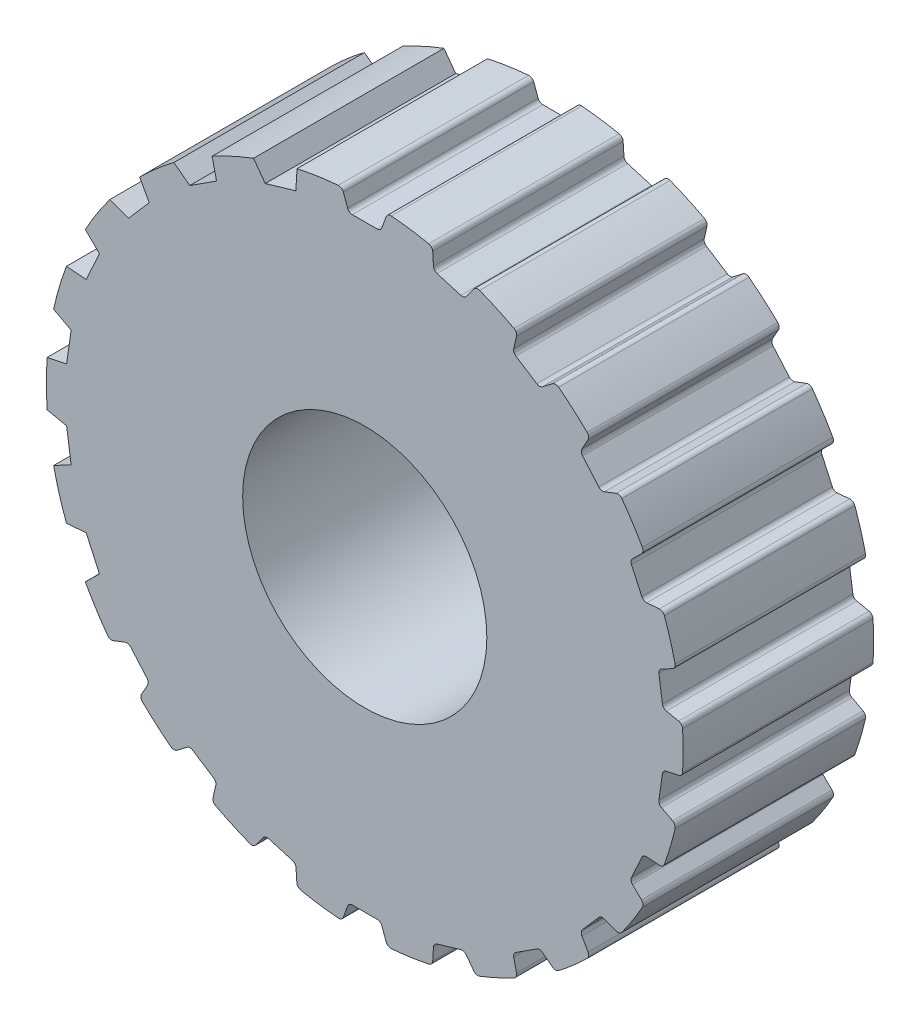
SolidWorks part; units mm, degrees
ref_plane "Front Plane" through (0, 0, 0) normal (0, 0, 1) x (1, 0, 0)
ref_plane "Top Plane" through (0, 0, 0) normal (0, 1, 0) x (1, 0, 0)
ref_plane "Right Plane" through (0, 0, 0) normal (1, 0, 0) x (0, 0, -1)
sketch "Sketch1" plane through (0, 0, 0) normal (0, 1, 0) x (1, 0, 0)
  line L0 (0, 36.1296) -> (0, -19.4741) construction
sketch "Sketch7" plane through (0, 0, 0) normal (0, 0, 1) x (1, 0, 0)
  line L0 (0, 0) -> (0, 31.56) construction
  line L1 (-2.325, 32.515) -> (-2.9401, 34.205) construction
  line L2 (-2.325, 32.515) -> (-1.6298, 30.605) construction
  line L3 (-1.6298, 30.605) -> (1.6298, 30.605) construction
  line L4 (1.6298, 30.605) -> (2.325, 32.515) construction
  line L5 (2.325, 32.515) -> (-2.325, 32.515) construction
  line L6 (0, 30.605) -> (0, 32.515) construction
  line L7 (2.325, 32.515) -> (2.9401, 34.205) construction
  line L8 (-2.9401, 34.205) -> (2.9401, 34.205) construction
  line L9 (0, 0) -> (8.8915, 30.2816) construction
  line L10 (8.8915, 30.2816) -> (9.1839, 31.2775) construction
  line L11 (0, 32.515) -> (0, 32.598) construction
  line L12 (0, 32.598) -> (0, 34.3311) construction
  line L13 (0, 33.4645) -> (9.428, 32.109) construction
  line L14 (9.1839, 31.2775) -> (9.6722, 32.9404) construction
  circle A1 centre (0, 0) radius 31.56 construction
  circle A2 centre (-1.2727, 31.115) radius 0.51 construction
  circle A3 centre (1.2727, 31.115) radius 0.51 construction
  circle A4 centre (0, 0) radius 32.598
  circle A5 centre (0, 0) radius 34.3311 construction
  dimension "D3" = 40
  dimension "D6" = 1.02
  dimension "D1" = 3.6
  dimension "D2" = 16.364
  dimension "D7" = 9.525
  dimension "D4" = 1.91
  dimension "D5" = 4.65
extrude "Boss-Extrude1" add sketch "Sketch7" along normal blind 7.25 and the other way blind 7.25 contours A4 region at (0, 0, 0)
sketch "Sketch14" plane through (0, 0, 0) normal (1, 0, 0) x (0, 0, -1)
  line L0 (-21.5, 0) -> (-21.5, 10)
  line L1 (-21.5, 0) -> (0, 0)
  line L2 (0, 0) -> (0, 19)
  line L3 (0, 19) -> (-7.25, 19)
  line L4 (-7.25, 19) -> (-21.5, 10)
  line L5 (-7.25, 32.598) -> (-7.25, -32.598) construction
  line L6 (-21.5, 7.0431) -> (-2.5683, 19) construction
  arc A0 (-7.25, 19) -> (-21.5, 10) centre (-21.2919, 25.4517) cw
  dimension "D1" = 10
  dimension "D2" = 19
  dimension "D3" = 21.5
  dimension "D4" = 2.5
revolve "Revolve1" add sketch "Sketch14" angle 360 about L0 region at (0, 7.3866, 9.0486) region at (0, 9.3218, 19.3148) region at (0, 17.2024, 6.8722)
sketch "Sketch9" plane through (0, 0, 0) normal (0, 0, 1) x (1, 0, 0)
  line L0 (2, 0) -> (-2, 0) construction
  line L1 (-2, 0) -> (-2, 7.5) construction
  line L2 (-2, 7.5) -> (2, 7.5) construction
  line L3 (2, 7.5) -> (2, 0) construction
  circle A0 centre (0, 0) radius 6 construction
  dimension "D1" = 12
  dimension "D2" = 4
  dimension "D3" = 7.5
sketch "Sketch10" plane through (0, 0, 0) normal (0, 0, 1) x (1, 0, 0)
  line L0 (2, 0) -> (-2, 0) construction
  line L1 (-2.2, 7.7) -> (2.2, 7.7)
  line L2 (-2.2, 7.7) -> (-2.2, 0)
  line L3 (-2.2, 0) -> (2.2, 0)
  line L4 (2.2, 7.7) -> (2.2, 0)
  line L5 (-2, 7.5) -> (2, 7.5) construction
  line L6 (2, 7.5) -> (2, 0) construction
  circle A0 centre (0, 0) radius 6.2
  circle A1 centre (0, 0) radius 6 construction
  dimension "D1" = 0.2
  dimension "D2" = 0.2
  dimension "D3" = 0.2
extrude "Cut-Extrude3" cut sketch "Sketch10" against normal through all both and the other way through all contours A0 L4 L1 L2 | L2 A0 L4 L3 | L4 A0 L2 L3 region at (0, 6.8793, 0) region at (0, 3.0348, 0) region at (0, -0.8613, 0)
sketch "Sketch11" plane through (0, 0, 0) normal (0, 1, 0) x (1, 0, 0)
  line L0 (32.598, 7.25) -> (-32.598, 7.25) construction
  line L1 (11, 7.25) -> (17.5, 7.25)
  line L2 (11, 7.25) -> (11, 4.75)
  line L3 (11, 4.75) -> (17.5, 4.75)
  line L4 (17.5, 7.25) -> (17.5, 4.75)
  line L5 (-32.598, -7.25) -> (32.598, -7.25) construction
  line L6 (11, -7.25) -> (17.5, -7.25)
  line L7 (11, -7.25) -> (11, -4.75)
  line L8 (11, -4.75) -> (17.5, -4.75)
  line L9 (17.5, -7.25) -> (17.5, -4.75)
  line L11 (11, 4.75) -> (11, -4.75) construction
  line L12 (17.5, -4.75) -> (17.5, 4.75) construction
  line L13 (6.2, 7.25) -> (-6.2, 7.25) construction
  line L14 (0, 7.25) -> (22.5, 7.25)
  line L15 (0, 7.25) -> (0, -7.25)
  line L16 (0, -7.25) -> (22.5, -7.25)
  line L17 (22.5, 7.25) -> (22.5, -7.25)
  line L18 (-6.2, -7.25) -> (6.2, -7.25) construction
  line L19 (6, 7.25) -> (6, -7.25) construction
  dimension "D1" = 22.5
  dimension "D2" = 6
  dimension "D3" = 5
  dimension "D4" = 5
  dimension "D5" = 2.5
revolve "Cut-Revolve1" [suppressed] cut sketch "Sketch11" angle 360 about L0
sketch "Sketch15" plane through (0, 0, -7.25) normal (0, 0, -1) x (-1, 0, 0)
  circle A0 centre (0, 0) radius 8.0081
  circle A1 centre (0, 0) radius 2.25
  dimension "D1" = 4.5
extrude "Boss-Extrude2" add sketch "Sketch15" against normal blind 5.5
sketch "Sketch16" plane through (0, 0, -7.25) normal (0, 0, -1) x (-1, 0, 0)
  circle A0 centre (0, 0) radius 5
  dimension "D1" = 10
extrude "Cut-Extrude4" cut sketch "Sketch16" against normal blind 3
sketch "Sketch17" plane through (0, 0, -7.25) normal (0, 0, -1) x (-1, 0, 0)
  circle A0 centre (0, 0) radius 32.598
  circle A1 centre (0, 0) radius 32.598 construction
  circle A2 centre (0, 0) radius 5
  circle A3 centre (0, 0) radius 5 construction
extrude "Boss-Extrude3" add sketch "Sketch17" along normal blind 7.5
sketch "Sketch8" plane through (0, 0, 0) normal (0, 0, 1) x (1, 0, 0)
  line L6 (-1.6298, 30.605) -> (-2.3552, 32.598)
  line L7 (-2.3552, 32.598) -> (2.3552, 32.598)
  line L8 (2.3552, 32.598) -> (1.6298, 30.605)
  line L9 (1.6298, 30.605) -> (-1.6298, 30.605)
  line L10 (-2.325, 32.515) -> (-1.6298, 30.605) construction
  line L11 (1.6298, 30.605) -> (2.325, 32.515) construction
  line L12 (7.0586, 29.8244) -> (6.9241, 31.9411)
  line L13 (6.9241, 31.9411) -> (11.4437, 30.614)
  line L14 (11.4437, 30.614) -> (10.1862, 28.9061)
  line L15 (10.1862, 28.9061) -> (7.0586, 29.8244)
  line L16 (15.1752, 26.6277) -> (15.6425, 28.6965)
  line L17 (15.6425, 28.6965) -> (19.6051, 26.1498)
  line L18 (19.6051, 26.1498) -> (17.9174, 24.8654)
  line L19 (17.9174, 24.8654) -> (15.1752, 26.6277)
  line L20 (22.0624, 21.2737) -> (23.0936, 23.1271)
  line L21 (23.0936, 23.1271) -> (26.1782, 19.5672)
  line L22 (26.1782, 19.5672) -> (24.197, 18.8103)
  line L23 (24.197, 18.8103) -> (22.0624, 21.2737)
  line L24 (27.1622, 14.1963) -> (28.6738, 15.6841)
  line L25 (28.6738, 15.6841) -> (30.6306, 11.3993)
  line L26 (30.6306, 11.3993) -> (28.5163, 11.2312)
  line L27 (28.5163, 11.2312) -> (27.1622, 14.1963)
  line L28 (30.0615, 5.9688) -> (31.931, 6.9704)
  line L29 (31.931, 6.9704) -> (32.6014, 2.3079)
  line L30 (32.6014, 2.3079) -> (30.5254, 2.7423)
  line L31 (30.5254, 2.7423) -> (30.0615, 5.9688)
  line L32 (30.5254, -2.7423) -> (32.6014, -2.3079)
  line L33 (32.6014, -2.3079) -> (31.931, -6.9704)
  line L34 (31.931, -6.9704) -> (30.0615, -5.9688)
  line L35 (30.0615, -5.9688) -> (30.5254, -2.7423)
  line L36 (28.5163, -11.2312) -> (30.6306, -11.3993)
  line L37 (30.6306, -11.3993) -> (28.6738, -15.6841)
  line L38 (28.6738, -15.6841) -> (27.1622, -14.1963)
  line L39 (27.1622, -14.1963) -> (28.5163, -11.2312)
  line L40 (24.197, -18.8103) -> (26.1782, -19.5672)
  line L41 (26.1782, -19.5672) -> (23.0936, -23.1271)
  line L42 (23.0936, -23.1271) -> (22.0624, -21.2737)
  line L43 (22.0624, -21.2737) -> (24.197, -18.8103)
  line L44 (17.9174, -24.8654) -> (19.6051, -26.1498)
  line L45 (19.6051, -26.1498) -> (15.6425, -28.6965)
  line L46 (15.6425, -28.6965) -> (15.1752, -26.6277)
  line L47 (15.1752, -26.6277) -> (17.9174, -24.8654)
  line L48 (10.1862, -28.9061) -> (11.4437, -30.614)
  line L49 (11.4437, -30.614) -> (6.9241, -31.9411)
  line L50 (6.9241, -31.9411) -> (7.0586, -29.8244)
  line L51 (7.0586, -29.8244) -> (10.1862, -28.9061)
  line L52 (1.6298, -30.605) -> (2.3552, -32.598)
  line L53 (2.3552, -32.598) -> (-2.3552, -32.598)
  line L54 (-2.3552, -32.598) -> (-1.6298, -30.605)
  line L55 (-1.6298, -30.605) -> (1.6298, -30.605)
  line L56 (-7.0586, -29.8244) -> (-6.9241, -31.9411)
  line L57 (-6.9241, -31.9411) -> (-11.4437, -30.614)
  line L58 (-11.4437, -30.614) -> (-10.1862, -28.9061)
  line L59 (-10.1862, -28.9061) -> (-7.0586, -29.8244)
  line L60 (-15.1752, -26.6277) -> (-15.6425, -28.6965)
  line L61 (-15.6425, -28.6965) -> (-19.6051, -26.1498)
  line L62 (-19.6051, -26.1498) -> (-17.9174, -24.8654)
  line L63 (-17.9174, -24.8654) -> (-15.1752, -26.6277)
  line L64 (-22.0624, -21.2737) -> (-23.0936, -23.1271)
  line L65 (-23.0936, -23.1271) -> (-26.1782, -19.5672)
  line L66 (-26.1782, -19.5672) -> (-24.197, -18.8103)
  line L67 (-24.197, -18.8103) -> (-22.0624, -21.2737)
  line L68 (-27.1622, -14.1963) -> (-28.6738, -15.6841)
  line L69 (-28.6738, -15.6841) -> (-30.6306, -11.3993)
  line L70 (-30.6306, -11.3993) -> (-28.5163, -11.2312)
  line L71 (-28.5163, -11.2312) -> (-27.1622, -14.1963)
  line L72 (-30.0615, -5.9688) -> (-31.931, -6.9704)
  line L73 (-31.931, -6.9704) -> (-32.6014, -2.3079)
  line L74 (-32.6014, -2.3079) -> (-30.5254, -2.7423)
  line L75 (-30.5254, -2.7423) -> (-30.0615, -5.9688)
  line L76 (-30.5254, 2.7423) -> (-32.6014, 2.3079)
  line L77 (-32.6014, 2.3079) -> (-31.931, 6.9704)
  line L78 (-31.931, 6.9704) -> (-30.0615, 5.9688)
  line L79 (-30.0615, 5.9688) -> (-30.5254, 2.7423)
  line L80 (-28.5163, 11.2312) -> (-30.6306, 11.3993)
  line L81 (-30.6306, 11.3993) -> (-28.6738, 15.6841)
  line L82 (-28.6738, 15.6841) -> (-27.1622, 14.1963)
  line L83 (-27.1622, 14.1963) -> (-28.5163, 11.2312)
  line L84 (-24.197, 18.8103) -> (-26.1782, 19.5672)
  line L85 (-26.1782, 19.5672) -> (-23.0936, 23.1271)
  line L86 (-23.0936, 23.1271) -> (-22.0624, 21.2737)
  line L87 (-22.0624, 21.2737) -> (-24.197, 18.8103)
  line L88 (-17.9174, 24.8654) -> (-19.6051, 26.1498)
  line L89 (-19.6051, 26.1498) -> (-15.6425, 28.6965)
  line L90 (-15.6425, 28.6965) -> (-15.1752, 26.6277)
  line L91 (-15.1752, 26.6277) -> (-17.9174, 24.8654)
  line L92 (-10.1862, 28.9061) -> (-11.4437, 30.614)
  line L93 (-11.4437, 30.614) -> (-6.9241, 31.9411)
  line L94 (-6.9241, 31.9411) -> (-7.0586, 29.8244)
  line L95 (-7.0586, 29.8244) -> (-10.1862, 28.9061)
  circle A0 centre (0, 0) radius 32.598 construction
  point P119 (0, 0)
  dimension "D1" = 22
extrude "Cut-Extrude2" cut sketch "Sketch8" against normal through all both and the other way through all
fillet "Fillet2" radius 0.51 60 edges at (-26.0957, -19.5357, -3.75) (-23.0506, -23.0499, -3.75) (-19.5348, -26.0963, -3.75) (-15.623, -28.6103, -3.75) (-11.3913, -30.5429, -3.75) (-6.9297, -31.8529, -3.75) (-2.325, -32.515, -3.75) (2.325, -32.515, -3.75) (6.9297, -31.8529, -3.75) (11.3913, -30.5429, -3.75) (15.623, -28.6103, -3.75) (19.5348, -26.0963, -3.75) (23.0506, -23.0499, -3.75) (26.0957, -19.5357, -3.75) (28.6108, -15.6221, -3.75) (30.5425, -11.3923, -3.75) (31.8531, -6.9287, -3.75) (32.5149, -2.326, -3.75) (32.5149, 2.326, -3.75) (31.8531, 6.9287, -3.75) (30.5425, 11.3923, -3.75) (28.6108, 15.6221, -3.75) (26.0957, 19.5357, -3.75) (23.0506, 23.0499, -3.75) (19.5348, 26.0963, -3.75) (15.623, 28.6103, -3.75) (11.3913, 30.5429, -3.75) (6.9297, 31.8529, -3.75) (2.325, 32.515, -3.75) (-24.197, -18.8103, -3.75) (-22.0624, -21.2737, -3.75) (-17.9174, -24.8654, -3.75) (-15.1752, -26.6277, -3.75) (-10.1862, -28.9061, -3.75) (-7.0586, -29.8244, -3.75) (-1.6298, -30.605, -3.75) (1.6298, -30.605, -3.75) (7.0586, -29.8244, -3.75) (10.1862, -28.9061, -3.75) (15.1752, -26.6277, -3.75) (17.9174, -24.8654, -3.75) (22.0624, -21.2737, -3.75) (24.197, -18.8103, -3.75) (27.1622, -14.1963, -3.75) (28.5163, -11.2312, -3.75) (30.0615, -5.9688, -3.75) (30.5254, -2.7423, -3.75) (30.5254, 2.7423, -3.75) (30.0615, 5.9688, -3.75) (28.5163, 11.2312, -3.75) (27.1622, 14.1963, -3.75) (24.197, 18.8103, -3.75) (22.0624, 21.2737, -3.75) (17.9174, 24.8654, -3.75) (15.1752, 26.6277, -3.75) (10.1862, 28.9061, -3.75) (7.0586, 29.8244, -3.75) (1.6298, 30.605, -3.75) (-1.6298, 30.605, -3.75) (-2.325, 32.515, -3.75)
sketch "Sketch18" plane through (0, 0, -14.75) normal (0, 0, -1) x (-1, 0, 0)
  circle A0 centre (0, 0) radius 5
  circle A1 centre (0, 0) radius 37.598
  circle A2 centre (0, 0) radius 32.598
  circle A3 centre (0, 0) radius 5 construction
  arc A4 (-2.7142, 32.4848) -> (-6.5477, 31.9336) centre (0, 0) ccw construction
  dimension "D1" = 5
extrude "Boss-Extrude4" add sketch "Sketch18" along normal blind 2.5 contours A1 A2 | A2 A0 region at (36.5346, 0, -14.75) region at (31.676, 0, -14.75)
sketch "Sketch19" plane through (0, 0, 7.25) normal (0, 0, 1) x (1, 0, 0)
  circle A0 centre (0, 0) radius 19
  circle A1 centre (0, 0) radius 37.598
  circle A2 centre (0, 0) radius 37.598 construction
  circle A3 centre (0, 0) radius 19 construction
extrude "Boss-Extrude5" add sketch "Sketch19" against normal blind 2.5
fillet "Fillet3" radius 0.5 19 edges at (2.2, 5.7966, 9.875) (-2.2, 5.7966, 9.875) (2.2, 6.7483, 21.5) (-2.2, 6.7483, 21.5) (0, 7.7, 21.5) (-19, 0, 7.25) (-10, 0, 21.5) (0, -6.2, 21.5) (-5, 0, -4.25) (-2.25, 0, -4.25) (-2.2, 6.7483, -1.75) (2.2, 6.7483, -1.75) (37.598, 0, 4.75) (-37.598, 0, -14.75) (-37.598, 0, -17.25) (37.598, 0, 7.25) (0, 7.7, -1.75) (0, -6.2, -1.75) (-5, 0, -17.25)
sketch "Sketch20" plane through (0, 0, 0) normal (1, 0, 0) x (0, 0, -1)
  line L0 (-4.75, -37.098) -> (-4.75, 37.098) construction
  line L1 (-21.5, 37.598) -> (17.25, 37.598)
  line L2 (-21.5, 37.598) -> (-21.5, -37.598)
  line L3 (-21.5, -37.598) -> (17.25, -37.598)
  line L4 (17.25, 37.598) -> (17.25, -37.598)
  line L5 (14.75, -37.598) -> (-4.75, -37.598)
  line L6 (14.75, -37.598) -> (14.75, 37.598)
  line L7 (14.75, 37.598) -> (-4.75, 37.598)
  line L8 (-4.75, -37.598) -> (-4.75, 37.598)
  line L9 (14.75, 37.098) -> (14.75, -37.098) construction
  line L10 (15.25, -37.598) -> (16.75, -37.598) construction
  line L11 (-21.5, 9.5013) -> (-21.5, -9.5013) construction
  line L12 (17.25, -37.098) -> (17.25, 37.098) construction
extrude "Cut-Extrude5" cut sketch "Sketch20" against normal through all both and the other way through all contours L3 L8 L1 L2 | L6 L3 L4 L1 region at (0, 0, 13.125) region at (0, 0, -16)
sketch "Sketch21" plane through (0, 0, 0) normal (0, 0, 1) x (1, 0, 0)
  circle A0 centre (0, 0) radius 12.5
  dimension "D1" = 25
extrude "Cut-Extrude6" cut sketch "Sketch21" against normal through all both and the other way through all
